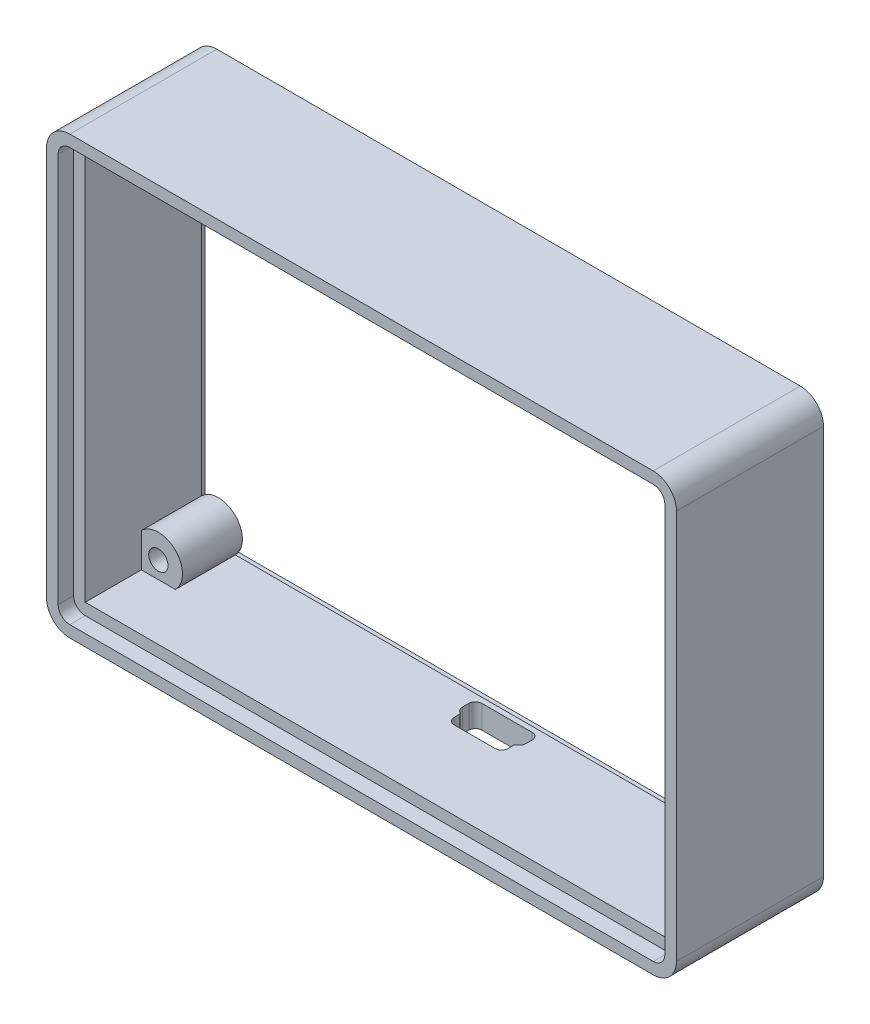
SolidWorks part; units mm, degrees
ref_plane "Front Plane" through (0, 0, 0) normal (0, 0, 1) x (1, 0, 0)
ref_plane "Top Plane" through (0, 0, 0) normal (0, 1, 0) x (1, 0, 0)
ref_plane "Right Plane" through (0, 0, 0) normal (1, 0, 0) x (0, 0, -1)
sketch "Sketch1" plane through (0, 0, 0) normal (0, 0, 1) x (1, 0, 0)
  line L0 (28.1649, 25.9244) -> (-47.2351, 25.9244)
  line L1 (-47.2351, 25.9244) -> (-47.2351, -24.4756)
  line L2 (-47.2351, -24.4756) -> (28.1649, -24.4756)
  line L3 (28.1649, -24.4756) -> (28.1649, 25.9244)
  line L4 (-47.0351, -24.2756) -> (27.9649, -24.2756)
  line L5 (27.9649, -24.2756) -> (27.9649, 25.7244)
  line L6 (27.9649, 25.7244) -> (-47.0351, 25.7244)
  line L7 (-47.0351, 25.7244) -> (-47.0351, -24.2756)
  line L8 (-47.0351, -24.2756) -> (27.9649, -24.2756) construction
  line L9 (27.9649, -24.2756) -> (27.9649, 25.7244) construction
  line L10 (27.9649, 25.7244) -> (-47.0351, 25.7244) construction
  line L11 (-47.0351, 25.7244) -> (-47.0351, -24.2756) construction
  line L12 (31.1649, 28.9244) -> (-50.2351, 28.9244)
  line L13 (-50.2351, 28.9244) -> (-50.2351, -27.4756)
  line L14 (-50.2351, -27.4756) -> (31.1649, -27.4756)
  line L15 (31.1649, -27.4756) -> (31.1649, 28.9244)
  dimension "D1" = 0
  dimension "D2" = 0.2
  dimension "D3" = 3
extrude "Boss-Extrude1" add sketch "Sketch1" against normal blind 27 from offset 2 contours L14 L15 L12 L13 L3 L2 L1 L0 region at (30.1746, 0.7244, 0) offset against normal yes
fillet "Fillet1" radius 3 4 edges at (-50.2351, 28.9244, -15.5) (-50.2351, -27.4756, -15.5) (31.1649, 28.9244, -15.5) (31.1649, -27.4756, -15.5)
sketch "Sketch2" plane through (0, 0, -2) normal (0, 0, 1) x (1, 0, 0)
  line L9 (28.1649, 27.4244) -> (-47.2351, 27.4244)
  line L10 (-48.7351, 25.9244) -> (-48.7351, -24.4756)
  line L11 (-47.2351, -25.9756) -> (28.1649, -25.9756)
  line L12 (29.6649, -24.4756) -> (29.6649, 25.9244)
  line L13 (28.1649, 27.4244) -> (-47.2351, 27.4244)
  line L14 (-48.7351, 25.9244) -> (-48.7351, -24.4756)
  line L15 (-47.2351, -25.9756) -> (28.1649, -25.9756)
  line L16 (29.6649, -24.4756) -> (29.6649, 25.9244)
  circle A4 centre (25.9649, 23.7244) radius 1.3 construction
  circle A5 centre (-45.0351, 23.7244) radius 1.3 construction
  circle A6 centre (-45.0351, -22.2756) radius 1.3 construction
  circle A7 centre (25.9649, -22.2756) radius 1.3 construction
  arc A8 (-47.2351, 27.4244) -> (-48.7351, 25.9244) centre (-47.2351, 25.9244) ccw
  arc A9 (-48.7351, -24.4756) -> (-47.2351, -25.9756) centre (-47.2351, -24.4756) ccw
  arc A10 (28.1649, -25.9756) -> (29.6649, -24.4756) centre (28.1649, -24.4756) ccw
  arc A11 (29.6649, 25.9244) -> (28.1649, 27.4244) centre (28.1649, 25.9244) ccw
  arc A12 (-47.2351, 27.4244) -> (-48.7351, 25.9244) centre (-47.2351, 25.9244) ccw
  arc A13 (-48.7351, -24.4756) -> (-47.2351, -25.9756) centre (-47.2351, -24.4756) ccw
  arc A14 (28.1649, -25.9756) -> (29.6649, -24.4756) centre (28.1649, -24.4756) ccw
  arc A15 (29.6649, 25.9244) -> (28.1649, 27.4244) centre (28.1649, 25.9244) ccw
  circle A16 centre (25.9649, 23.7244) radius 1.3
  circle A17 centre (-45.0351, 23.7244) radius 1.3
  circle A18 centre (-45.0351, -22.2756) radius 1.3
  circle A19 centre (25.9649, -22.2756) radius 1.3
  dimension "D1" = 1.5
extrude "Cut-Extrude1" cut sketch "Sketch2" against normal blind 2 contours A19 | L13 A12 L14 A13 L15 A14 L16 A15 region at (25.9649, -22.2756, -2)
extrude "Cut-Extrude2" cut sketch "Sketch2<3>" along normal blind 10 from surface starting at face at (-9.5351, 0.7244, -29)
sketch "Sketch2<3>" plane through (0, 0, -2) normal (0, 0, 1) x (1, 0, 0) same geometry as "Sketch2"
sketch "Sketch3" plane through (0, 0, -4) normal (0, 0, 1) x (1, 0, 0)
  line L9 (-45.0351, 23.7244) -> (-45.0351, -22.2756) construction
  line L10 (-45.0351, -22.2756) -> (25.9649, -22.2756) construction
  line L11 (25.9649, -22.2756) -> (25.9649, 23.7244) construction
  line L12 (25.9649, 23.7244) -> (-45.0351, 23.7244) construction
  line L13 (28.1649, -24.4756) -> (28.1649, 25.9244)
  line L14 (-47.2351, -24.4756) -> (28.1649, -24.4756)
  line L15 (-47.2351, 25.9244) -> (-47.2351, -24.4756)
  line L16 (28.1649, 25.9244) -> (-47.2351, 25.9244)
  line L17 (28.1649, -24.4756) -> (28.1649, 25.9244)
  line L18 (-47.2351, -24.4756) -> (28.1649, -24.4756)
  line L19 (-47.2351, 25.9244) -> (-47.2351, -24.4756)
  line L20 (28.1649, 25.9244) -> (-47.2351, 25.9244)
  circle A0 centre (-45.0351, -22.2756) radius 1.25
  circle A1 centre (-45.0351, 23.7244) radius 1.25
  circle A2 centre (25.9649, 23.7244) radius 1.25
  circle A3 centre (25.9649, -22.2756) radius 1.25
  circle A4 centre (-45.0351, -22.2756) radius 3.1113
  circle A5 centre (-45.0351, 23.7244) radius 3.1113
  circle A6 centre (25.9649, -22.2756) radius 3.1113
  circle A7 centre (25.9649, 23.7244) radius 3.1113
  line M28 (28.1649, 25.9244) -> (28.1649, -24.4756)
  line M29 (28.1649, -24.4756) -> (-47.2351, -24.4756)
  line M30 (-47.2351, -24.4756) -> (-47.2351, 25.9244)
  line M31 (-47.2351, 25.9244) -> (28.1649, 25.9244)
  dimension "D1" = 2.5
  dimension "D2" = 0
  dimension "D3" = 2.2
extrude "Boss-Extrude2" add sketch "Sketch3" against normal up to surface (15 mm away) from offset 7.25 contours L18 A4 A0 M30 | A5 A1 M30 M31 | A7 A2 M31 M28 | L17 A6 A3 M29 region at (25.9649, -24.4005, -4) region at (23.818, 21.5775, -4) region at (-45.0351, -24.4005, -4) region at (-42.2301, 24.8862, -4) up to face at (-9.5351, 0.7244, -19) offset against normal yes
sketch "Sketch5" plane through (0, -27.4756, 0) normal (0, -1, 0) x (1, 0, 0)
  line L0 (-10.2851, -18.3125) -> (-3.7851, -18.3125)
  line L1 (-2.9351, -17.4625) -> (-2.9351, -16.6425)
  line L2 (-3.2777, -15.9606) -> (-3.4897, -15.8028)
  line L3 (-3.5501, -15.6825) -> (-3.5501, -14.9625)
  line L4 (-4.4001, -14.1125) -> (-9.6701, -14.1125)
  line L5 (-10.5201, -14.9625) -> (-10.5201, -15.6825)
  line L6 (-10.5806, -15.8028) -> (-10.7926, -15.9606)
  line L7 (-11.1351, -16.6425) -> (-11.1351, -17.4625)
  line L8 (-10.2851, -18.0625) -> (-3.7851, -18.0625)
  line L9 (-3.1851, -17.4625) -> (-3.1851, -16.6425)
  line L10 (-3.4269, -16.1611) -> (-3.6389, -16.0034)
  line L11 (-3.8001, -15.6825) -> (-3.8001, -14.9625)
  line L12 (-4.4001, -14.3625) -> (-9.6701, -14.3625)
  line L13 (-10.2701, -14.9625) -> (-10.2701, -15.6825)
  line L14 (-10.4313, -16.0034) -> (-10.6433, -16.1611)
  line L15 (-10.8851, -16.6425) -> (-10.8851, -17.4625)
  line L16 (-10.2851, -18.0625) -> (-3.7851, -18.0625) construction
  line L17 (-3.1851, -17.4625) -> (-3.1851, -16.6425) construction
  line L18 (-3.4269, -16.1611) -> (-3.6389, -16.0034) construction
  line L19 (-3.8001, -15.6825) -> (-3.8001, -14.9625) construction
  line L20 (-4.4001, -14.3625) -> (-9.6701, -14.3625) construction
  line L21 (-10.2701, -14.9625) -> (-10.2701, -15.6825) construction
  line L22 (-10.4313, -16.0034) -> (-10.6433, -16.1611) construction
  line L23 (-10.8851, -16.6425) -> (-10.8851, -17.4625) construction
  arc A0 (-10.8851, -17.4625) -> (-10.2851, -18.0625) centre (-10.2851, -17.4625) ccw
  arc A1 (-3.7851, -18.0625) -> (-3.1851, -17.4625) centre (-3.7851, -17.4625) ccw
  arc A2 (-3.1851, -16.6425) -> (-3.4269, -16.1611) centre (-3.7851, -16.6425) ccw
  arc A3 (-3.8001, -15.6825) -> (-3.6389, -16.0034) centre (-3.4001, -15.6825) ccw
  arc A4 (-3.8001, -14.9625) -> (-4.4001, -14.3625) centre (-4.4001, -14.9625) ccw
  arc A5 (-9.6701, -14.3625) -> (-10.2701, -14.9625) centre (-9.6701, -14.9625) ccw
  arc A6 (-10.4313, -16.0034) -> (-10.2701, -15.6825) centre (-10.6701, -15.6825) ccw
  arc A7 (-10.6433, -16.1611) -> (-10.8851, -16.6425) centre (-10.2851, -16.6425) ccw
  arc A8 (-10.8851, -17.4625) -> (-10.2851, -18.0625) centre (-10.2851, -17.4625) ccw construction
  arc A9 (-3.7851, -18.0625) -> (-3.1851, -17.4625) centre (-3.7851, -17.4625) ccw construction
  arc A10 (-3.1851, -16.6425) -> (-3.4269, -16.1611) centre (-3.7851, -16.6425) ccw construction
  arc A11 (-3.8001, -15.6825) -> (-3.6389, -16.0034) centre (-3.4001, -15.6825) ccw construction
  arc A12 (-3.8001, -14.9625) -> (-4.4001, -14.3625) centre (-4.4001, -14.9625) ccw construction
  arc A13 (-9.6701, -14.3625) -> (-10.2701, -14.9625) centre (-9.6701, -14.9625) ccw construction
  arc A14 (-10.4313, -16.0034) -> (-10.2701, -15.6825) centre (-10.6701, -15.6825) ccw construction
  arc A15 (-10.6433, -16.1611) -> (-10.8851, -16.6425) centre (-10.2851, -16.6425) ccw construction
  arc A16 (-3.7851, -18.3125) -> (-2.9351, -17.4625) centre (-3.7851, -17.4625) ccw
  arc A17 (-2.9351, -16.6425) -> (-3.2777, -15.9606) centre (-3.7851, -16.6425) ccw
  arc A18 (-3.5501, -15.6825) -> (-3.4897, -15.8028) centre (-3.4001, -15.6825) ccw
  arc A19 (-3.5501, -14.9625) -> (-4.4001, -14.1125) centre (-4.4001, -14.9625) ccw
  arc A20 (-9.6701, -14.1125) -> (-10.5201, -14.9625) centre (-9.6701, -14.9625) ccw
  arc A21 (-10.5806, -15.8028) -> (-10.5201, -15.6825) centre (-10.6701, -15.6825) ccw
  arc A22 (-10.7926, -15.9606) -> (-11.1351, -16.6425) centre (-10.2851, -16.6425) ccw
  arc A23 (-11.1351, -17.4625) -> (-10.2851, -18.3125) centre (-10.2851, -17.4625) ccw
  dimension "D1" = 0
extrude "Cut-Extrude3" cut sketch "Sketch5" against normal blind 28.2 contours L0 A16 L1 A17 L2 A18 L3 A19 L4 A20 L5 A21 L6 A22 L7 A23
sketch "Sketch6" plane through (0, 0, -29) normal (0, 0, -1) x (-1, 0, 0)
  line L4 (50.2351, -24.4756) -> (50.2351, 25.9244)
  line L5 (47.2351, 28.9244) -> (-28.1649, 28.9244)
  line L6 (-31.1649, 25.9244) -> (-31.1649, -24.4756)
  line L7 (-28.1649, -27.4756) -> (47.2351, -27.4756)
  line L8 (50.2351, -24.4756) -> (50.2351, 25.9244)
  line L9 (47.2351, 28.9244) -> (-28.1649, 28.9244)
  line L10 (-31.1649, 25.9244) -> (-31.1649, -24.4756)
  line L11 (-28.1649, -27.4756) -> (47.2351, -27.4756)
  line L12 (-29.6649, 25.9244) -> (-29.6649, -24.4756)
  line L13 (47.2351, 27.4244) -> (-28.1649, 27.4244)
  line L14 (48.7351, -24.4756) -> (48.7351, 25.9244)
  line L15 (-28.1649, -25.9756) -> (47.2351, -25.9756)
  line L16 (-29.6649, 25.9244) -> (-29.6649, -24.4756)
  line L17 (47.2351, 27.4244) -> (-28.1649, 27.4244)
  line L18 (48.7351, -24.4756) -> (48.7351, 25.9244)
  line L19 (-28.1649, -25.9756) -> (47.2351, -25.9756)
  arc A4 (50.2351, 25.9244) -> (47.2351, 28.9244) centre (47.2351, 25.9244) ccw
  arc A5 (-28.1649, 28.9244) -> (-31.1649, 25.9244) centre (-28.1649, 25.9244) ccw
  arc A6 (-31.1649, -24.4756) -> (-28.1649, -27.4756) centre (-28.1649, -24.4756) ccw
  arc A7 (47.2351, -27.4756) -> (50.2351, -24.4756) centre (47.2351, -24.4756) ccw
  arc A8 (50.2351, 25.9244) -> (47.2351, 28.9244) centre (47.2351, 25.9244) ccw
  arc A9 (-28.1649, 28.9244) -> (-31.1649, 25.9244) centre (-28.1649, 25.9244) ccw
  arc A10 (-31.1649, -24.4756) -> (-28.1649, -27.4756) centre (-28.1649, -24.4756) ccw
  arc A11 (47.2351, -27.4756) -> (50.2351, -24.4756) centre (47.2351, -24.4756) ccw
  arc A12 (-28.1649, 27.4244) -> (-29.6649, 25.9244) centre (-28.1649, 25.9244) ccw
  arc A13 (48.7351, 25.9244) -> (47.2351, 27.4244) centre (47.2351, 25.9244) ccw
  arc A14 (47.2351, -25.9756) -> (48.7351, -24.4756) centre (47.2351, -24.4756) ccw
  arc A15 (-29.6649, -24.4756) -> (-28.1649, -25.9756) centre (-28.1649, -24.4756) ccw
  arc A16 (-28.1649, 27.4244) -> (-29.6649, 25.9244) centre (-28.1649, 25.9244) ccw
  arc A17 (48.7351, 25.9244) -> (47.2351, 27.4244) centre (47.2351, 25.9244) ccw
  arc A18 (47.2351, -25.9756) -> (48.7351, -24.4756) centre (47.2351, -24.4756) ccw
  arc A19 (-29.6649, -24.4756) -> (-28.1649, -25.9756) centre (-28.1649, -24.4756) ccw
  dimension "D1" = 0
  dimension "D2" = 0
extrude "Cut-Extrude4" cut sketch "Sketch6" against normal blind 8
